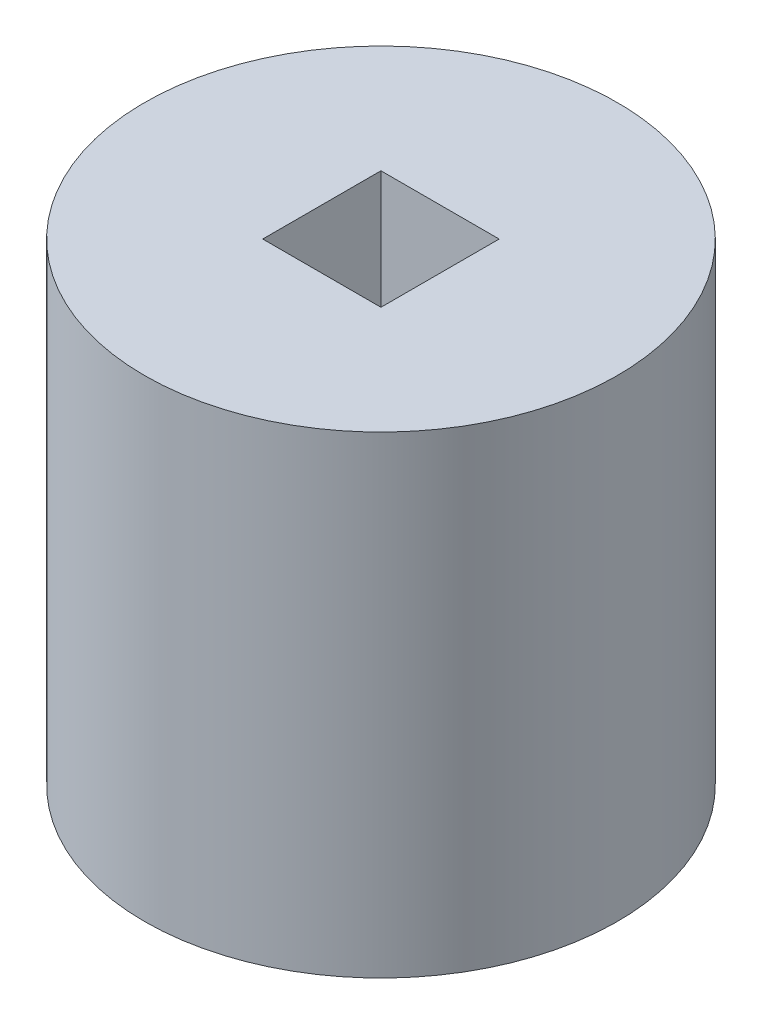
SolidWorks part; units mm, degrees
ref_plane "Front Plane" through (0, 0, 0) normal (0, 0, 1) x (1, 0, 0)
ref_plane "Top Plane" through (0, 0, 0) normal (0, 1, 0) x (1, 0, 0)
ref_plane "Right Plane" through (0, 0, 0) normal (1, 0, 0) x (0, 0, -1)
sketch "Sketch3" plane through (0, 0, 0) normal (0, 1, 0) x (1, 0, 0)
  line L1 (-12.5, 12.5) -> (12.5, 12.5)
  line L2 (-12.5, 12.5) -> (-12.5, -12.5)
  line L3 (-12.5, -12.5) -> (12.5, -12.5)
  line L4 (12.5, 12.5) -> (12.5, -12.5)
  line L5 (-12.5, 12.5) -> (12.5, -12.5) construction
  line L6 (-12.5, -12.5) -> (12.5, 12.5) construction
  circle A0 centre (0, 0) radius 50
  dimension "D1" = 25
  dimension "D2" = 25
extrude "Boss-Extrude1" add sketch "Sketch3" along normal blind 100
ref_axis "Axis2" through (0, 100, 0) along (0, -1, 0)
ref_point "Point3"
